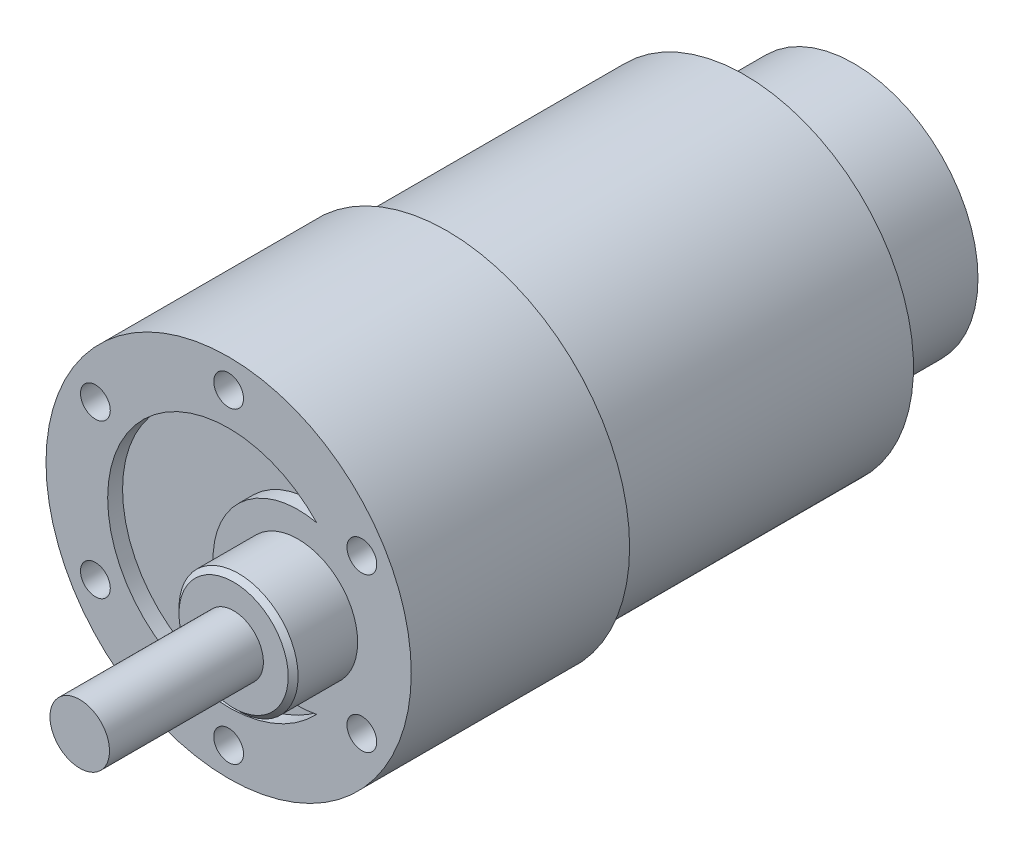
SolidWorks part; units mm, degrees
ref_plane "Front Plane" through (0, 0, 0) normal (0, 0, 1) x (1, 0, 0)
ref_plane "Top Plane" through (0, 0, 0) normal (0, 1, 0) x (1, 0, 0)
ref_plane "Right Plane" through (0, 0, 0) normal (1, 0, 0) x (0, 0, -1)
ref_plane "Plane1" through (0, 0, 0) normal (0, -1, 0) x (1, 0, 0)
sketch "Sketch1" plane through (0, 0, 0) normal (0, -1, 0) x (1, 0, 0)
  line L0 (18.4, 52) -> (0, 52)
  line L1 (0, 52) -> (0, 29)
  line L2 (0, 29) -> (17, 29)
  line L3 (16, 30) -> (18.4, 30)
  line L4 (18.4, 30) -> (18.4, 52)
  line L5 (0, 52) -> (0, 29) construction
  arc A0 (17, 29) -> (16, 30) centre (16, 29) ccw
revolve "Revolve1" add sketch "Sketch1" angle 360 about L5 reverse direction yes
sketch "Sketch2" plane through (0, 0, 29) normal (0, 0, -1) x (-1, 0, 0)
  circle A0 centre (0, 0) radius 17
extrude "Boss-Extrude1" add sketch "Sketch2" along normal blind 29
sketch "Sketch3" plane through (0, 0, 0) normal (0, 0, -1) x (-1, 0, 0)
  circle A0 centre (0, 0) radius 12.5
extrude "Boss-Extrude2" add sketch "Sketch3" along normal blind 11
sketch "Sketch4" plane through (0, 0, 52) normal (0, 0, 1) x (1, 0, 0)
  arc A0 (8.8681, 8.3597) -> (8.8681, -8.3597) centre (0, 0) ccw
  arc A1 (8.8681, -8.3597) -> (8.8681, 8.3597) centre (7, 0) cw
extrude "Cut-Extrude1" cut sketch "Sketch4" against normal blind 1.5
sketch "Sketch5" plane through (0, 0, 0) normal (0, -1, 0) x (1, 0, 0)
  line L0 (10, 74) -> (7, 74)
  line L1 (7, 74) -> (7, 52)
  line L2 (7, 52) -> (13, 52)
  line L3 (13, 52) -> (13, 58.5)
  line L4 (13, 58.5) -> (10, 58.5)
  line L5 (10, 58.5) -> (10, 74)
  line L6 (7, 74) -> (7, 52) construction
revolve "Revolve2" add sketch "Sketch5" angle 360 about L6 reverse direction yes
hole_wizard "Ø3.0 (3) Diameter Hole1" positions "Sketch7" profile "Sketch6" hole size "Ø3.0" standard "Ansi Metric"
sketch "Sketch7" plane through (0, 0, 52) normal (0, 0, 1) x (1, 0, 0)
  point P0 (-13.4234, 7.75)
  point P1 (-13.4234, -7.75)
  point P2 (0, -15.5)
  point P3 (13.4234, -7.75)
  point P4 (13.4234, 7.75)
  point P5 (0, 15.5)
sketch "Sketch6" plane through (-13.4234, 7.75, 52) normal (1, 0, 0) x (0, -1, 0)
  line L0 (0, 0) -> (0, 3)
  line L1 (0, 3) -> (1.5, 3)
  line L2 (1.5, 3) -> (1.5, 0)
  line L5 (1.5, 0) -> (0, 0)
  line L10 (0, 3) -> (-1.5, 3) construction
  line L11 (0, -6.35) -> (0, 107.95) construction
  dimension "Hole Dia." = 3
  dimension "Hole Depth" = 3
  dimension "Drill Angle" = 180
chamfer "Chamfer1" distance 0.5 angle 45 1 edges at (1, 0, 58.5)
